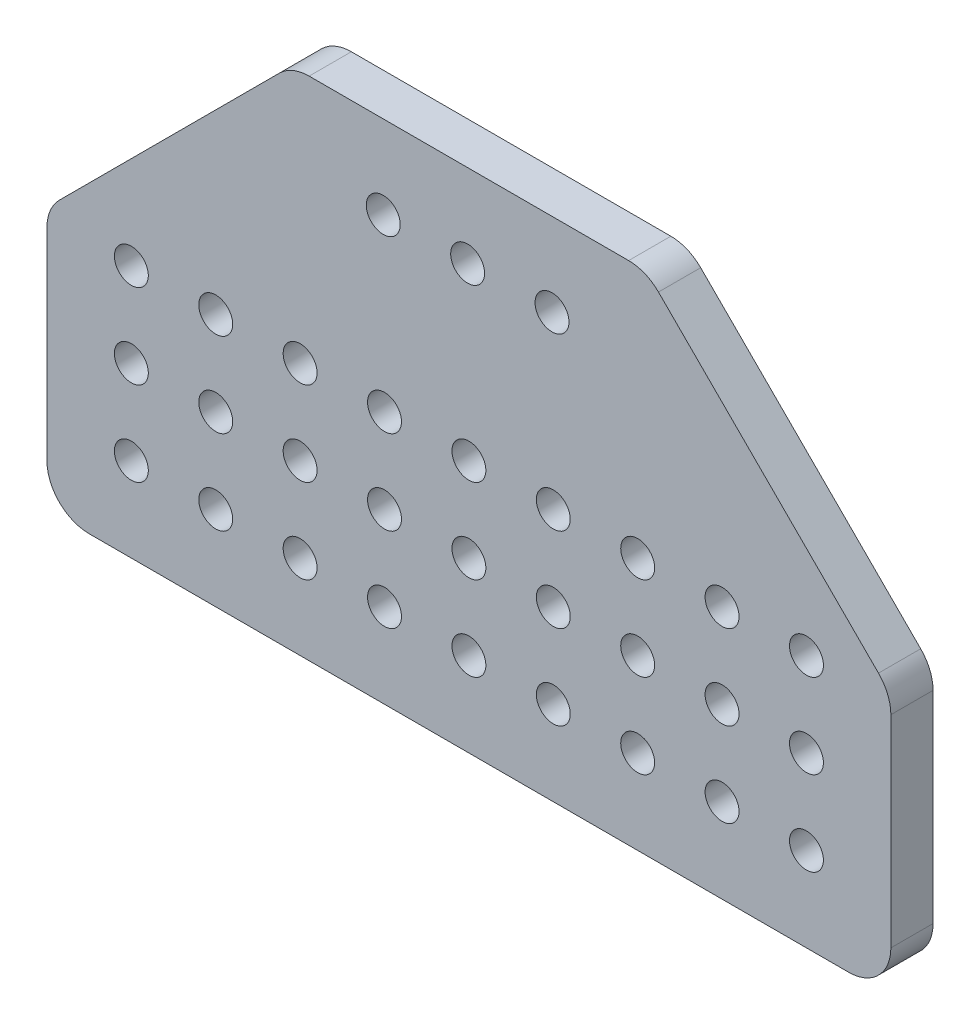
SolidWorks part; units mm, degrees
material "6061-T6 (SS)"
ref_plane "Front Plane" through (0, 0, 0) normal (0, 0, 1) x (1, 0, 0)
ref_plane "Top Plane" through (0, 0, 0) normal (0, 1, 0) x (1, 0, 0)
ref_plane "Right Plane" through (0, 0, 0) normal (1, 0, 0) x (0, 0, -1)
sketch "Sketch1" plane through (0, 0, 0) normal (0, 0, 1) x (1, 0, 0)
  line L1 (0, 0) -> (127, 0)
  line L2 (0, 0) -> (0, 82.55)
  line L3 (0, 82.55) -> (127, 82.55)
  line L4 (127, 0) -> (127, 82.55)
  dimension "D1" = 82.55
  dimension "D2" = 127
extrude "Boss-Extrude1" add sketch "Sketch1" along normal blind 6.35
sketch "Sketch2" plane through (0, 0, 0) normal (0, 0, -1) x (-1, 0, 0)
  line L0 (-127, 82.55) -> (0, 82.55) construction
  line L1 (0, 82.55) -> (0, 0) construction
  circle A0 centre (-76.0095, 63.6905) radius 2.5527
  circle A1 centre (-63.3095, 63.6905) radius 2.5527
  circle A2 centre (-50.6095, 63.6905) radius 2.5527
  dimension "D1" = 18.8595
  dimension "D2" = 12.7
  dimension "D3" = 12.7
  dimension "D4" = 50.6095
  dimension "D5" = 18.8595
  dimension "D6" = 18.8595
  dimension "D7" = 5.1054
  dimension "D8" = 5.1054
  dimension "D9" = 5.1054
extrude "Cut-Extrude1" cut sketch "Sketch2" against normal through all and the other way through all
sketch "Sketch3" plane through (0, 0, 0) normal (0, 0, -1) x (-1, 0, 0)
  line L0 (-127, 0) -> (-127, 82.55) construction
  line L1 (0, 0) -> (-127, 0) construction
  circle A0 centre (-114.3, 38.1) radius 2.5527
  circle A1 centre (-114.3, 25.4) radius 2.5527
  circle A2 centre (-114.3, 12.7) radius 2.5527
  circle A3 centre (-101.6, 38.1) radius 2.5527
  circle A4 centre (-101.6, 25.4) radius 2.5527
  circle A5 centre (-101.6, 12.7) radius 2.5527
  circle A6 centre (-88.9, 38.1) radius 2.5527
  circle A7 centre (-88.9, 25.4) radius 2.5527
  circle A8 centre (-88.9, 12.7) radius 2.5527
  circle A9 centre (-76.2, 38.1) radius 2.5527
  circle A10 centre (-76.2, 25.4) radius 2.5527
  circle A11 centre (-76.2, 12.7) radius 2.5527
  circle A12 centre (-63.5, 38.1) radius 2.5527
  circle A13 centre (-63.5, 25.4) radius 2.5527
  circle A14 centre (-63.5, 12.7) radius 2.5527
  circle A15 centre (-50.8, 38.1) radius 2.5527
  circle A16 centre (-50.8, 25.4) radius 2.5527
  circle A17 centre (-50.8, 12.7) radius 2.5527
  circle A18 centre (-38.1, 38.1) radius 2.5527
  circle A19 centre (-38.1, 25.4) radius 2.5527
  circle A20 centre (-38.1, 12.7) radius 2.5527
  circle A21 centre (-25.4, 38.1) radius 2.5527
  circle A22 centre (-25.4, 25.4) radius 2.5527
  circle A23 centre (-25.4, 12.7) radius 2.5527
  circle A24 centre (-12.7, 38.1) radius 2.5527
  circle A25 centre (-12.7, 25.4) radius 2.5527
  circle A26 centre (-12.7, 12.7) radius 2.5527
  dimension "D1" = 5.1054
  dimension "D2" = 5.1054
  dimension "D3" = 5.1054
  dimension "D4" = 12.7
  dimension "D5" = 12.7
  dimension "D6" = 12.7
  dimension "D7" = 12.7
  dimension "D8" = 12.7
  dimension "D9" = 12.7
  dimension "D11" = 12.7
  dimension "D10" = 9
extrude "Cut-Extrude2" cut sketch "Sketch3" against normal through all
sketch "Sketch4" plane through (0, 0, 0) normal (0, 0, -1) x (-1, 0, 0)
  line L0 (-83.82, 82.55) -> (-127, 39.37)
  line L1 (-127, 82.55) -> (0, 82.55) construction
  line L2 (-127, 39.37) -> (-127, 82.55)
  line L3 (-127, 82.55) -> (-83.82, 82.55)
  line L4 (-43.18, 82.55) -> (0, 82.55)
  line L5 (0, 82.55) -> (0, 39.37)
  line L6 (0, 82.55) -> (0, 0) construction
  line L7 (0, 39.37) -> (-43.18, 82.55)
  dimension "D1" = 45
  dimension "D2" = 45
  dimension "D3" = 43.18
  dimension "D4" = 43.18
extrude "Cut-Extrude3" cut sketch "Sketch4" against normal through all
sketch "Sketch5" plane through (0, 0, 0) normal (0, 0, -1) x (-1, 0, 0)
  line L0 (-90.17, 76.2) -> (-36.83, 76.2)
  line L1 (-127, 39.37) -> (-83.82, 82.55) construction
  line L2 (-43.18, 82.55) -> (0, 39.37) construction
  line L3 (-36.83, 76.2) -> (-43.18, 82.55)
  line L4 (-43.18, 82.55) -> (-83.82, 82.55)
  line L5 (-83.82, 82.55) -> (-90.17, 76.2)
  dimension "D1" = 6.35
extrude "Cut-Extrude4" cut sketch "Sketch5" against normal through all
fillet "Fillet1" radius 6.35 6 edges at (127, 39.37, 3.175) (127, 0, 3.175) (0, 0, 3.175) (36.83, 76.2, 3.175) (90.17, 76.2, 3.175) (0, 39.37, 3.175)
